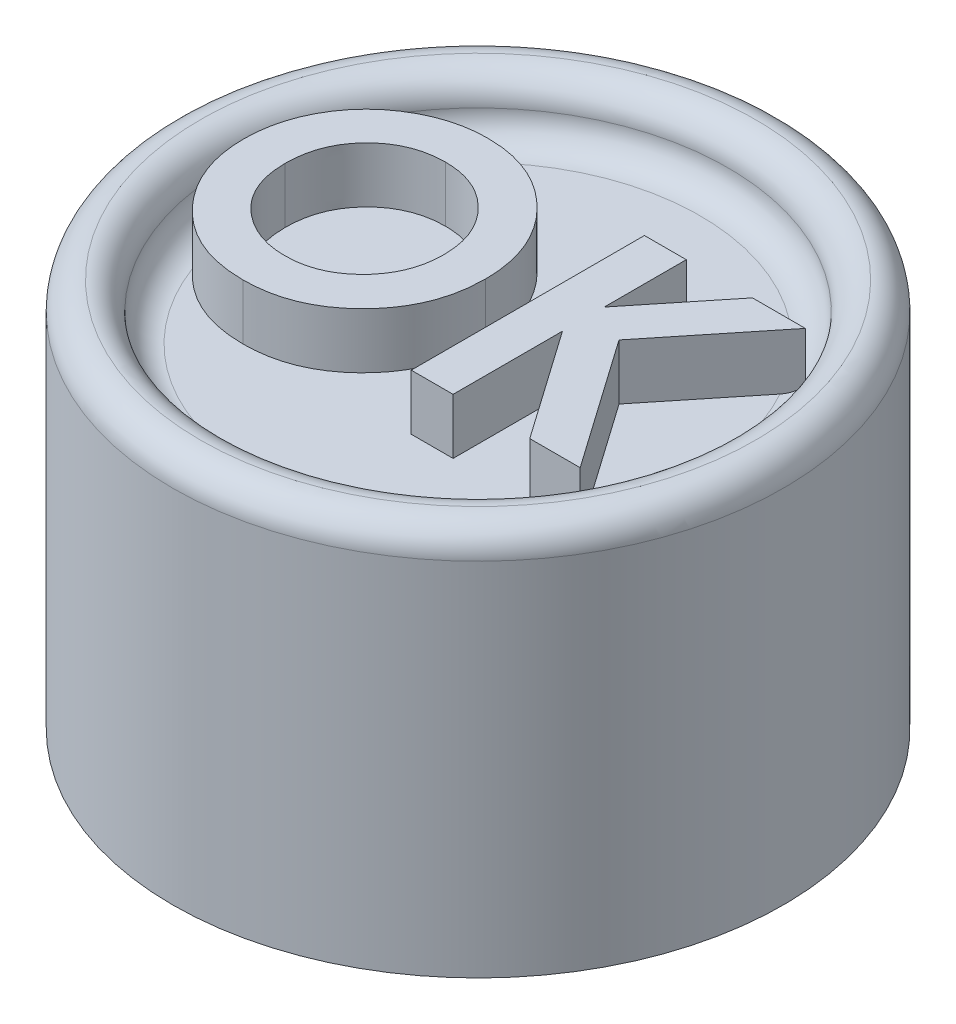
SolidWorks part; units mm, degrees
ref_plane "Спереди" through (0, 0, 0) normal (0, 0, 1) x (1, 0, 0)
ref_plane "Сверху" through (0, 0, 0) normal (0, 1, 0) x (1, 0, 0)
ref_plane "Справа" through (0, 0, 0) normal (1, 0, 0) x (0, 0, -1)
sketch "Эскиз1" plane through (0, 0, 0) normal (0, 1, 0) x (1, 0, 0)
  circle A0 centre (0, 0) radius 5.5
extrude "Бобышка-Вытянуть1" add sketch "Эскиз1" along normal blind 7
fillet "Скругление1" radius 0.5 1 edges at (0, 7, 5.5)
sketch "Эскиз2" plane through (0, 7, 0) normal (0, 1, 0) x (1, 0, 0)
  circle A0 centre (0, 0) radius 4.5
extrude "Вырез-Вытянуть1" cut sketch "Эскиз2" against normal blind 1
fillet "Скругление2" radius 0.5 1 edges at (0, 7, 4.5)
sketch "Эскиз3" plane through (0, 6, 0) normal (0, 1, 0) x (1, 0, 0)
  line L0 (-1000, 0) -> (49000, 0) construction
  line L1 (0, -1000) -> (0, 49000) construction
  line L4 (-1000, -4) -> (49000, -4) construction
  line L5 (-1000, 4) -> (49000, 4) construction
  line L6 (-4, -1000) -> (-4, 49000) construction
  line L7 (4, -1000) -> (4, 49000) construction
  circle A0 centre (0, 0) radius 5 construction
  text T0 "<b>OK</b>" font "Century Gothic" height 4.2
  point P6 (-4.6712, -2.1412)
  point P7 (0, 0)
  point P8 (0, 0)
  point P17 (-4.5064, -2.1662)
  point P20 (-4.5782, -2.01)
extrude "Бобышка-Вытянуть2" add sketch "Эскиз3" along normal blind 1
fillet "Скругление3" radius 0.5 1 edges at (0, 6, 4.5)
sketch "Эскиз5" plane through (0, 0, 0) normal (0, -1, 0) x (1, 0, 0)
  line L0 (0, -1000) -> (0, 49000) construction
  line L1 (-1000, 0) -> (49000, 0) construction
  line L2 (-2, -2) -> (2, -2)
  line L3 (2, -2) -> (2, 2)
  line L4 (-2, 2) -> (2, 2)
  line L5 (-2, -2) -> (-2, 2)
  line L7 (-2, -1000) -> (-2, 49000) construction
  line L8 (2, -1000) -> (2, 49000) construction
  line L9 (-1000, 2) -> (49000, 2) construction
  line L10 (-1000, -2) -> (49000, -2) construction
  dimension "D1" = 2
  dimension "D2" = 2
extrude "Вырез-Вытянуть2" cut sketch "Эскиз5" against normal blind 3
